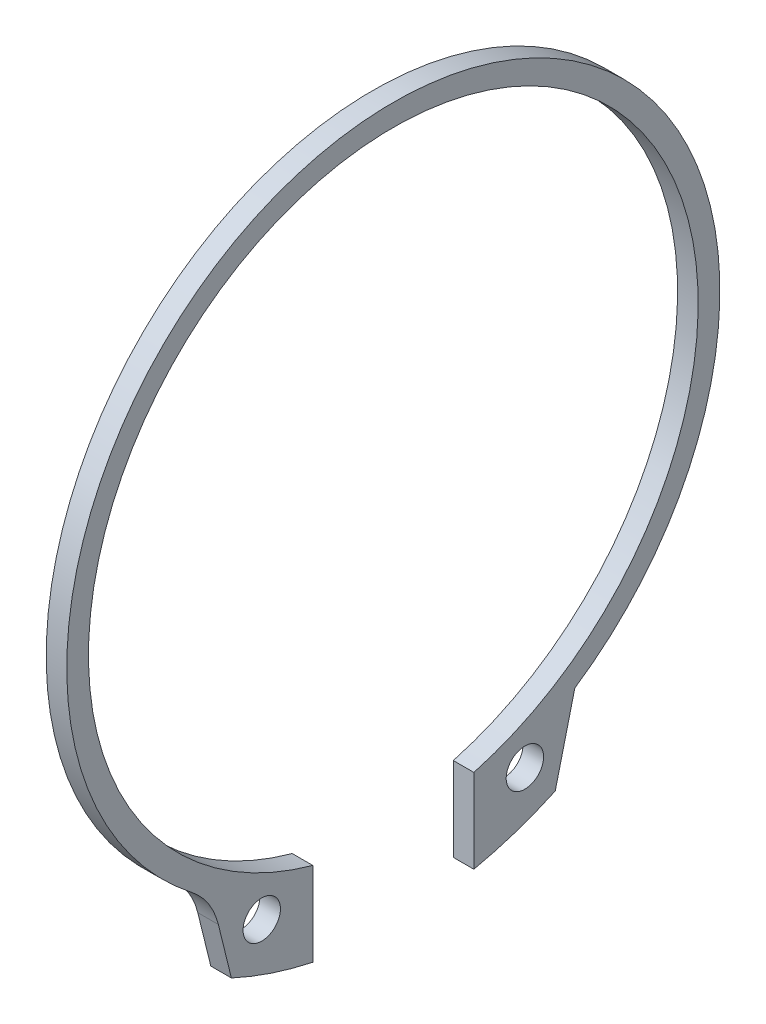
SolidWorks part; units mm, degrees
ref_plane "Front" through (0, 0, 0) normal (0, 0, 1) x (1, 0, 0)
ref_plane "Top" through (0, 0, 0) normal (0, 1, 0) x (1, 0, 0)
ref_plane "Right" through (0, 0, 0) normal (1, 0, 0) x (0, 0, -1)
sketch "Esquisse1" plane through (0, 0, 0) normal (1, 0, 0) x (0, 0, -1)
  line L0 (0, 0) -> (-10.7663, -39.302) construction
  line L1 (0, 0) -> (0, -72.5729) construction
  line L2 (-10.7663, -39.302) -> (-10.7663, -50.5154)
  line L3 (10.7663, -39.302) -> (10.7663, -50.5154)
  line L4 (-21.6444, -46.8961) -> (-23.3873, -39.8302)
  line L5 (21.6444, -46.8961) -> (24.2614, -36.2864)
  arc A1 (10.7663, -39.302) -> (-10.7663, -39.302) centre (0, 0) ccw
  arc A2 (24.2614, -36.2864) -> (-26.9274, -34.3546) centre (0, 0) ccw
  arc A4 (21.6444, -46.8961) -> (10.7663, -50.5154) centre (0, 0) cw
  arc A5 (-21.6444, -46.8961) -> (-10.7663, -50.5154) centre (0, 0) ccw
  circle A6 centre (-17.5869, -42.1556) radius 2.5
  circle A7 centre (17.5869, -42.1556) radius 2.5
  arc A8 (-23.3873, -39.8302) -> (-26.9274, -34.3546) centre (-33.0963, -42.2251) ccw
  arc A9 (23.3873, -39.8302) -> (26.9274, -34.3546) centre (33.0963, -42.2251) cw
  point P10 (10.7663, -39.302)
  point P13 (-21.6444, -46.8961)
  point P20 (-24.2614, -36.2864)
  dimension "D1" = 5
  dimension "D2" = 81.5
  dimension "D3" = 10
extrude "Boss.-Extru.1" add sketch "Esquisse1" along normal blind 2.75 contours A8 L4 A5 L2 A1 L3 A4 L5 A2 A6 A7 region at (0, -44.9087, 12.0503)
